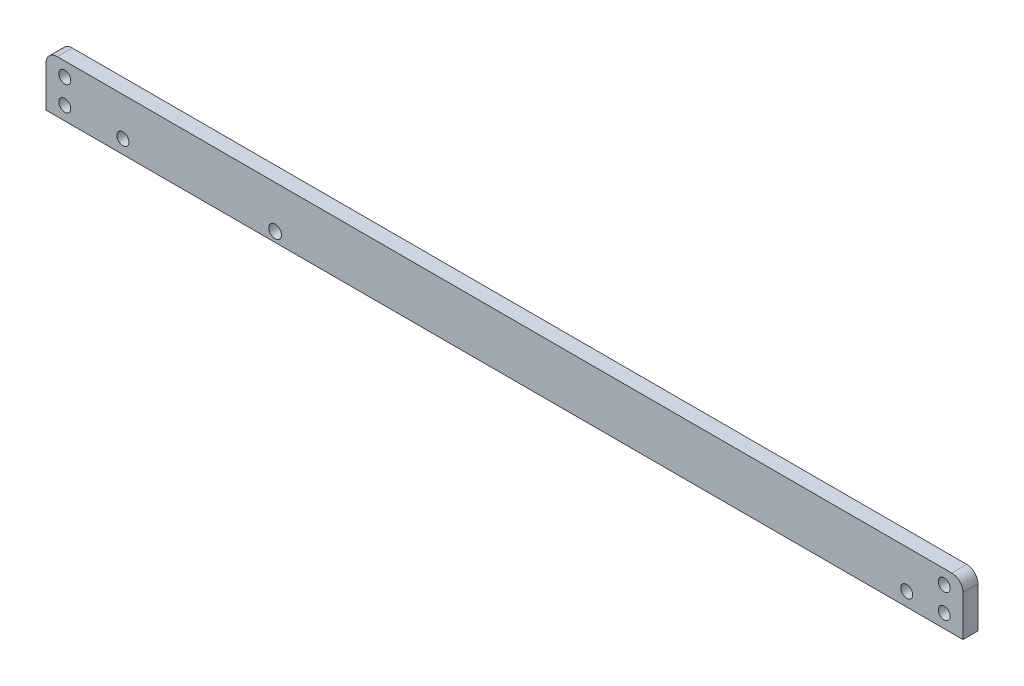
SolidWorks part; units mm, degrees
ref_plane "Front Plane" through (0, 0, 0) normal (0, 0, 1) x (1, 0, 0)
ref_plane "Top Plane" through (0, 0, 0) normal (0, 1, 0) x (1, 0, 0)
ref_plane "Right Plane" through (0, 0, 0) normal (1, 0, 0) x (0, 0, -1)
sketch "Sketch1" plane through (0, 0, 0) normal (0, 0, 1) x (1, 0, 0)
  line L3 (59.5711, 89.4051) -> (-178.9289, 89.4051)
  line L4 (-181.9289, 86.4051) -> (-181.9289, 75.5393)
  line L5 (62.5711, 75.5393) -> (62.5711, 86.4051)
  line L6 (62.5711, 75.5393) -> (-181.9289, 75.5393)
  arc A2 (62.5711, 86.4051) -> (59.5711, 89.4051) centre (59.5711, 86.4051) ccw
  arc A3 (-178.9289, 89.4051) -> (-181.9289, 86.4051) centre (-178.9289, 86.4051) ccw
extrude "Boss-Extrude1" add sketch "Sketch1" along normal blind 4
hole_wizard "M3 Clearance Hole1" positions "Sketch3" profile "Sketch2" hole size "M3" standard "ISO" end condition through all
sketch "Sketch3" plane through (0, 0, 4) normal (0, 0, 1) x (1, 0, 0)
  point P0 (-176.9289, 85.6728)
  point P2 (-176.9289, 79.1728)
  point P4 (-161.4289, 79.1728)
  point P6 (47.5711, 79.1728)
  point P8 (57.5711, 79.1728)
  point P10 (57.5711, 85.6728)
sketch "Sketch2" plane through (-176.9289, 85.6728, 4) normal (1, 0, 0) x (0, -1, 0)
  line L0 (0, 0) -> (0, 4)
  line L1 (0, 4) -> (1.6, 4)
  line L2 (1.6, 4) -> (1.6, 0)
  line L5 (1.6, 0) -> (0, 0)
  line L11 (0, -6.35) -> (0, 107.95) construction
  dimension "Thru Hole Dia." = 3.2
  dimension "Thru Hole Depth" = 4
hole_wizard "M3 Clearance Hole2" positions "Sketch4" profile "Sketch5" hole size "M3" standard "ISO" end condition through all
sketch "Sketch4" plane through (0, 0, 0) normal (0, 0, -1) x (-1, 0, 0)
  point P0 (120.8323, 78.0751)
sketch "Sketch5" plane through (-120.8323, 78.0751, 0) normal (1, 0, 0) x (0, 1, 0)
  line L0 (0, 0) -> (0, 4)
  line L1 (0, 4) -> (1.7, 4)
  line L2 (1.7, 4) -> (1.7, 0)
  line L5 (1.7, 0) -> (0, 0)
  line L11 (0, -6.35) -> (0, 107.95) construction
  dimension "Thru Hole Dia." = 3.4
  dimension "Thru Hole Depth" = 4
